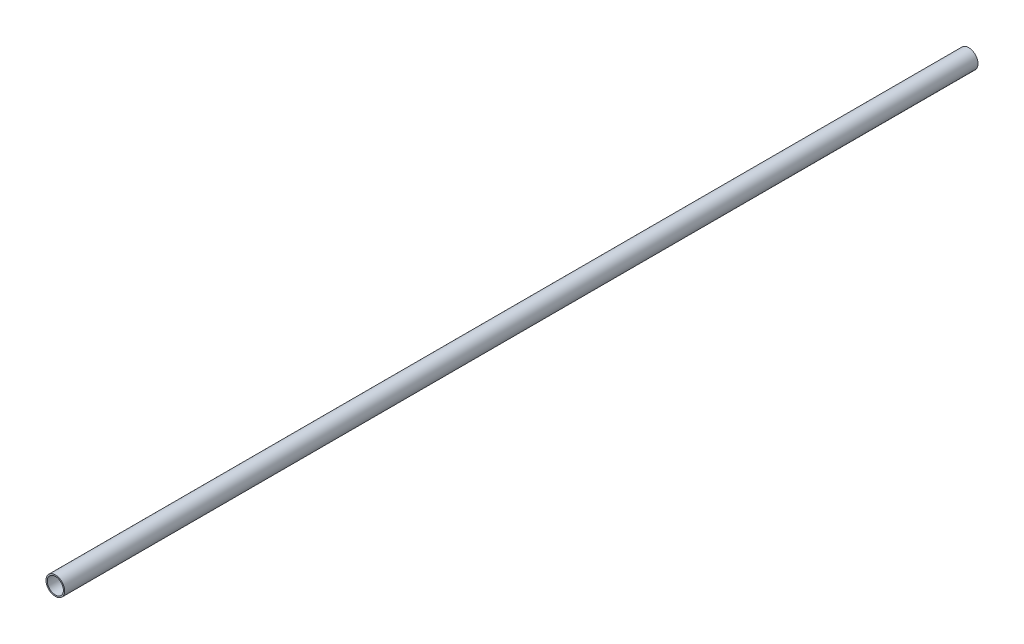
SolidWorks part; units mm, degrees
ref_plane "Front Plane" through (0, 0, 0) normal (0, 0, 1) x (1, 0, 0)
ref_plane "Top Plane" through (0, 0, 0) normal (0, 1, 0) x (1, 0, 0)
ref_plane "Right Plane" through (0, 0, 0) normal (1, 0, 0) x (0, 0, -1)
sketch "Sketch2" plane through (-549.704, -1576.7433, 0) normal (0, 0, -1) x (0.7833, -0.6217, 0)
  circle A6 centre (-549.704, -1576.7433) radius 4.7625
  circle A7 centre (-549.704, -1576.7433) radius 5.5245
  dimension "D1" = 9.525
  dimension "D2" = 11.049
extrude "Boss-Extrude1" add sketch "Sketch2" along normal blind 540.004
